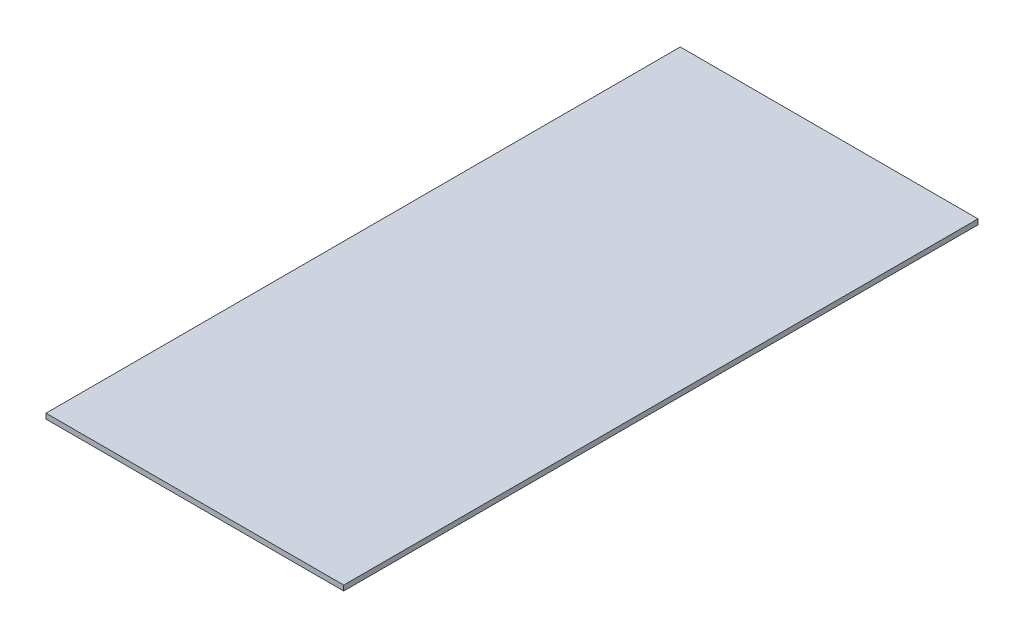
SolidWorks part; units mm, degrees
material "Glass"
ref_plane "Front Plane" through (0, 0, 0) normal (0, 0, 1) x (1, 0, 0)
ref_plane "Top Plane" through (0, 0, 0) normal (0, 1, 0) x (1, 0, 0)
ref_plane "Right Plane" through (0, 0, 0) normal (1, 0, 0) x (0, 0, -1)
sketch "Sketch1" plane through (0, 0, 0) normal (0, 1, 0) x (1, 0, 0)
  line L1 (-230, -490) -> (230, -490)
  line L2 (-230, -490) -> (-230, 490)
  line L3 (-230, 490) -> (230, 490)
  line L4 (230, -490) -> (230, 490)
  line L5 (-230, -490) -> (230, 490) construction
  line L6 (-230, 490) -> (230, -490) construction
  point P0 (0, 0)
  dimension "D1" = 980
  dimension "D2" = 460
extrude "Boss-Extrude1" add sketch "Sketch1" along normal mid plane 8
sketch "Sketch2" plane through (0, -4, 0) normal (0, -1, 0) x (1, 0, 0)
  line L0 (205.5, 3.3852) -> (-205.5, 3.3852) construction
  line L1 (-200, 270) -> (200, 270)
  line L2 (-200, 270) -> (-200, -230)
  line L3 (-200, -230) -> (200, -230)
  line L4 (200, 270) -> (200, -230)
  line L5 (-200, 270) -> (200, -230) construction
  line L6 (-200, -230) -> (200, 270) construction
  point P0 (0, 20)
  point P5 (0, 58.8038)
  point P9 (0, 3.3852)
  dimension "D1" = 20
  dimension "D2" = 500
  dimension "D3" = 400
split line "Split Line1"
